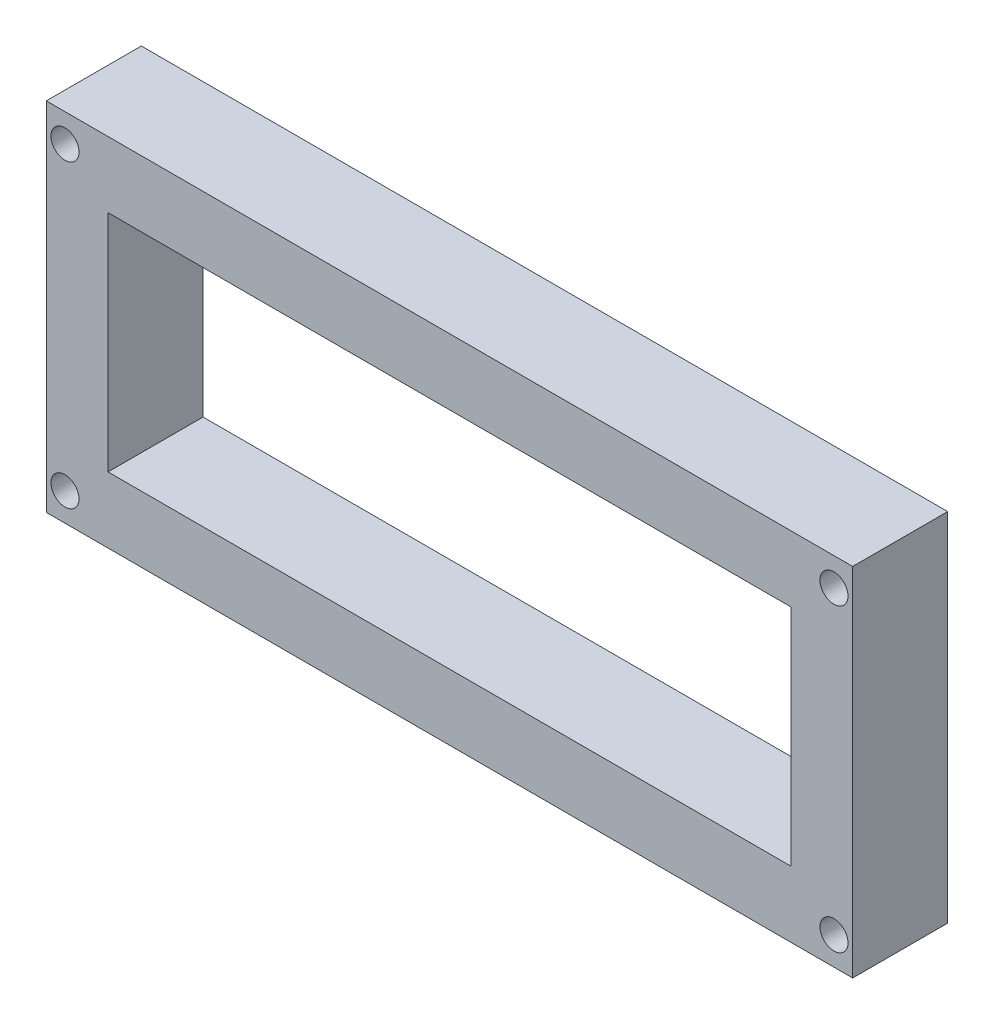
SolidWorks part; units mm, degrees
ref_plane "Front Plane" through (0, 0, 0) normal (0, 0, 1) x (1, 0, 0)
ref_plane "Top Plane" through (0, 0, 0) normal (0, 1, 0) x (1, 0, 0)
ref_plane "Right Plane" through (0, 0, 0) normal (1, 0, 0) x (0, 0, -1)
sketch "Sketch1" plane through (0, 0, 0) normal (0, 0, 1) x (1, 0, 0)
  line L1 (-43.1, 19.05) -> (43.1, 19.05)
  line L2 (-43.1, 19.05) -> (-43.1, -19.05)
  line L3 (-43.1, -19.05) -> (43.1, -19.05)
  line L4 (43.1, 19.05) -> (43.1, -19.05)
  line L5 (-36.5, 12) -> (36.5, 12)
  line L6 (-36.5, 12) -> (-36.5, -12)
  line L7 (-36.5, -12) -> (36.5, -12)
  line L8 (36.5, 12) -> (36.5, -12)
  point P4 (0, 19.05)
  point P5 (-43.1, 0)
  point P11 (0, 12)
  point P12 (-36.5, 0)
  dimension "D1" = 86.2
  dimension "D2" = 38.1
  dimension "D3" = 73
  dimension "D4" = 24
extrude "Boss-Extrude1" add sketch "Sketch1" along normal blind 10.16
sketch "Sketch2" plane through (0, 0, 10.16) normal (0, 0, 1) x (1, 0, 0)
  line L0 (43.1, -19.05) -> (43.1, 19.05) construction
  line L1 (43.1, 19.05) -> (-43.1, 19.05) construction
  line L2 (0, -55) -> (0, 55) construction
  line L4 (55, 0) -> (-55, 0) construction
  circle A1 centre (41.1, 16.05) radius 1.5
  circle A2 centre (-41.1, 16.05) radius 1.5
  circle A3 centre (-41.1, -16.05) radius 1.5
  circle A4 centre (41.1, -16.05) radius 1.5
  dimension "D1" = 2
  dimension "D3" = 3
  dimension "D2" = 3
extrude "Cut-Extrude1" cut sketch "Sketch2" against normal blind 10.16
